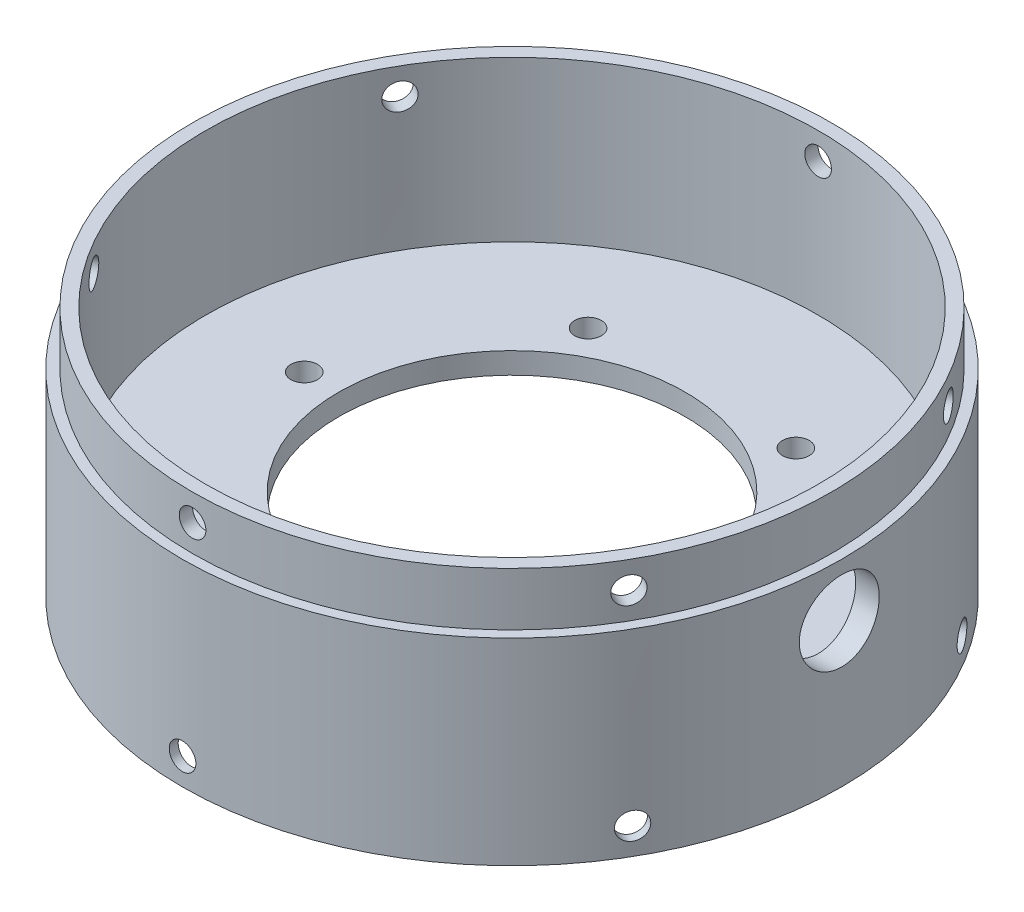
SolidWorks part; units mm, degrees
material "6061-T6 (SS)"
ref_plane "Front Plane" through (0, 0, 0) normal (0, 0, 1) x (1, 0, 0)
ref_plane "Top Plane" through (0, 0, 0) normal (0, 1, 0) x (1, 0, 0)
ref_plane "Right Plane" through (0, 0, 0) normal (1, 0, 0) x (0, 0, -1)
ref_axis "Axis1" through (0, 55, 0) along (0, -1, 0)
ref_plane "Plane1" through (0, 0, 0) normal (0.866, 0, 0.5) x (0, -1, 0)
sketch "Sketch3" plane through (0, 0, 0) normal (0, 1, 0) x (1, 0, 0)
  circle A0 centre (0, 0) radius 78.5876
  dimension "D1" = 157.1752
extrude "Boss-Extrude1" add sketch "Sketch3" along normal blind 2.54 and the other way blind 2.54
sketch "Sketch4" plane through (0, 2.54, 0) normal (0, 1, 0) x (1, 0, 0)
  circle A0 centre (0, 0) radius 78.5876
  circle A1 centre (0, 0) radius 73.025
  dimension "D1" = 157.1752
  dimension "D2" = 146.05
extrude "Boss-Extrude3" add sketch "Sketch4" along normal blind 25.4
sketch "Sketch5" plane through (0, 27.94, 0) normal (0, 1, 0) x (1, 0, 0)
  circle A0 centre (0, 0) radius 73.025
  circle A1 centre (0, 0) radius 73.025 construction
  circle A2 centre (0, 0) radius 76.2
  dimension "D1" = 152.4
extrude "Boss-Extrude4" add sketch "Sketch5" along normal blind 12.7
hole_wizard "1/4 (0.25) Diameter Hole1" positions "3DSketch1" profile "Sketch6" hole size "1/4" standard "ANSI Inch" end condition up to next
sketch3d "3DSketch1"
  point P0 (0, 34.29, 76.2)
  dimension "D1" = 6.35
sketch "Sketch6" plane through (0, 34.29, 76.2) normal (1, 0, 0) x (0, -1, 0)
  line L0 (0, 0) -> (0, 175.9554)
  line L1 (0, 175.9554) -> (3.175, 175.9554)
  line L2 (3.175, 175.9554) -> (3.175, 0)
  line L5 (3.175, 0) -> (0, 0)
  line L11 (0, -6.35) -> (0, 107.95) construction
  dimension "Thru Hole Dia." = 6.35
  dimension "Thru Hole Depth" = 175.9554
sketch "Sketch7" plane through (0, -2.54, 0) normal (0, -1, 0) x (1, 0, 0)
  circle A0 centre (0, 0) radius 73.025
  circle A1 centre (0, 0) radius 78.5876
  circle A2 centre (0, 0) radius 78.5876 construction
  circle A3 centre (0, 0) radius 73.025 construction
extrude "Boss-Extrude5" add sketch "Sketch7" along normal blind 3.81
sketch "Sketch8" plane through (0, -6.35, 0) normal (0, -1, 0) x (1, 0, 0)
  circle A0 centre (0, 0) radius 76.454
  circle A1 centre (0, 0) radius 78.5876
  circle A4 centre (0, 0) radius 78.5876 construction
  dimension "D1" = 152.908
extrude "Boss-Extrude6" add sketch "Sketch8" along normal blind 12.7
hole_wizard "1/4 (0.25) Diameter Hole2" positions "3DSketch2" profile "Sketch9" hole size "1/4" standard "ANSI Inch" end condition up to next
sketch3d "3DSketch2"
  point P0 (0, -12.7, 78.5876)
  dimension "D1" = 6.35
sketch "Sketch9" plane through (0, -12.7, 78.5876) normal (1, 0, 0) x (0, -1, 0)
  line L0 (0, 0) -> (0, 183.0271)
  line L1 (0, 183.0271) -> (3.175, 183.0271)
  line L2 (3.175, 183.0271) -> (3.175, 0)
  line L5 (3.175, 0) -> (0, 0)
  line L11 (0, -6.35) -> (0, 107.95) construction
  dimension "Thru Hole Dia." = 6.35
  dimension "Thru Hole Depth" = 183.0271
hole_wizard "1/4 (0.25) Diameter Hole3" positions "Sketch11" profile "Sketch12" hole size "1/4" standard "ANSI Inch" end condition up to next
sketch "Sketch11" plane through (0, 2.54, 0) normal (0, 1, 0) x (1, 0, 0)
  line L0 (-30.25, -52.3945) -> (30.25, 52.3945) construction
  point P0 (-24.765, -42.8942)
  dimension "D1" = 49.53
sketch "Sketch12" plane through (-24.765, 2.54, 42.8942) normal (1, 0, 0) x (0, 0, 1)
  line L0 (0, 0) -> (0, 5.081)
  line L1 (0, 5.081) -> (3.175, 5.081)
  line L2 (3.175, 5.081) -> (3.175, 0)
  line L5 (3.175, 0) -> (0, 0)
  line L11 (0, -6.35) -> (0, 107.95) construction
  dimension "Thru Hole Dia." = 6.35
  dimension "Thru Hole Depth" = 5.081
pattern_circular "CirPattern2" count 6 over 360 about axis through (0, 55, 0) along (0, -1, 0) of "1/4 (0.25) Diameter Hole1", "1/4 (0.25) Diameter Hole2", "1/4 (0.25) Diameter Hole3"
sketch "Sketch10" plane through (0, 2.54, 0) normal (0, 1, 0) x (1, 0, 0)
  circle A0 centre (0, 0) radius 41.275
  dimension "D1" = 82.55
extrude "Cut-Extrude2" cut sketch "Sketch10" against normal up to next
hole_wizard "3/4 (0.75) Diameter Hole1" positions "3DSketch3" profile "Sketch15" hole size "3/4" standard "ANSI Inch" end condition up to next
sketch3d "3DSketch3"
  point P0 (78.5876, 15.24, 0)
  dimension "D1" = 12.7
sketch "Sketch15" plane through (78.5876, 15.24, 0) normal (0, 1, 0) x (0, 0, -1)
  line L0 (0, 0) -> (0, 5.5626)
  line L1 (0, 5.5626) -> (9.525, 5.5626)
  line L2 (9.525, 5.5626) -> (9.525, 0)
  line L5 (9.525, 0) -> (0, 0)
  line L11 (0, -6.35) -> (0, 107.95) construction
  dimension "Thru Hole Dia." = 19.05
  dimension "Thru Hole Depth" = 5.5626
